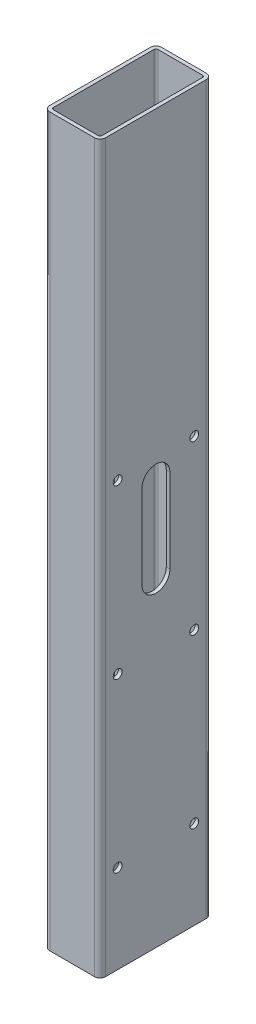
SolidWorks part; units mm, degrees
material "6061-T6 (SS)"
ref_plane "Front Plane" through (0, 0, 0) normal (0, 0, 1) x (1, 0, 0)
ref_plane "Top Plane" through (0, 0, 0) normal (0, 1, 0) x (1, 0, 0)
ref_plane "Right Plane" through (0, 0, 0) normal (1, 0, 0) x (0, 0, -1)
sketch "Sketch1" plane through (0, 0, 0) normal (0, 1, 0) x (1, 0, 0)
  line L1 (10.16, -25.4) -> (-10.16, -25.4)
  line L2 (12.7, -22.86) -> (12.7, 22.86)
  line L3 (10.16, 25.4) -> (-10.16, 25.4)
  line L4 (-12.7, -22.86) -> (-12.7, 22.86)
  line L5 (12.7, -25.4) -> (-12.7, 25.4) construction
  line L6 (12.7, 25.4) -> (-12.7, -25.4) construction
  arc A0 (-10.16, -25.4) -> (-12.7, -22.86) centre (-10.16, -22.86) cw
  arc A1 (10.16, -25.4) -> (12.7, -22.86) centre (10.16, -22.86) ccw
  arc A2 (12.7, 22.86) -> (10.16, 25.4) centre (10.16, 22.86) ccw
  arc A3 (-10.16, 25.4) -> (-12.7, 22.86) centre (-10.16, 22.86) ccw
  point P0 (0, 0)
  dimension "D3" = 2.54
  dimension "D1" = 25.4
  dimension "D2" = 50.8
extrude "Extrude-Thin1" add sketch "Sketch1" against normal blind 330.2 thin thin type one direction reverse wall 1.651
sketch "Sketch2" plane through (-12.7, 0, 0) normal (-1, 0, 0) x (0, 0, 1)
  line L0 (0, -146.2416) -> (0, -281.392) construction
  line L3 (-262.7767, -420.7745) -> (-262.7767, -434.1095) construction
  line L4 (6.6675, -146.2416) -> (6.6675, -281.392)
  line L5 (-6.6675, -146.2416) -> (-6.6675, -281.392)
  line L6 (-263.9645, -427.442) -> (-128.814, -427.442) construction
  line L7 (-128.814, -427.442) -> (0, -151.1994) construction
  line L8 (0, -275.042) -> (-263.9645, -427.442) construction
  line L10 (-122.464, -420.7745) -> (-270.3145, -420.7745) construction
  line L11 (-270.3145, -434.1095) -> (-122.464, -434.1095) construction
  arc A2 (6.6675, -146.2416) -> (-6.6675, -146.2416) centre (0, -146.2416) ccw
  arc A3 (-6.6675, -281.392) -> (6.6675, -281.392) centre (0, -281.392) ccw
  point P3 (0, -213.8168)
  point P18 (-262.7767, -427.442)
  dimension "D5" = 13.335
  dimension "D2" = 65
  dimension "D3" = 30
  dimension "D4" = 304.8
  dimension "D6" = 6.35
extrude "Cut-Extrude1" cut sketch "Sketch2" against normal up to next
sketch "Sketch5" plane through (12.7, 0, 0) normal (1, 0, 0) x (0, 0, -1)
  line L0 (0, -146.2416) -> (0, -184.3416) construction
  line L1 (6.35, -146.2416) -> (6.35, -184.3416)
  line L2 (-6.35, -146.2416) -> (-6.35, -184.3416)
  arc A0 (6.35, -146.2416) -> (-6.35, -146.2416) centre (0, -146.2416) ccw
  arc A1 (-6.35, -184.3416) -> (6.35, -184.3416) centre (0, -184.3416) ccw
  arc A2 (6.6675, -146.2416) -> (-6.6675, -146.2416) centre (0, -146.2416) ccw construction
  point P2 (0, -165.2916)
  dimension "D1" = 6.35
  dimension "D2" = 38.1
extrude "Cut-Extrude4" cut sketch "Sketch5" against normal up to next
sketch "Sketch4" plane through (12.7, 0, 0) normal (1, 0, 0) x (0, 0, -1)
  circle A0 centre (-17.399, -290.0168) radius 2.0193 construction
  circle A1 centre (17.399, -290.0168) radius 2.0193 construction
  circle A2 centre (-17.399, -213.8168) radius 2.0193 construction
  circle A3 centre (17.399, -213.8168) radius 2.0193 construction
  circle A4 centre (-17.399, -137.6168) radius 2.0193 construction
  circle A5 centre (17.399, -137.6168) radius 2.0193 construction
  circle A6 centre (-17.399, -290.0168) radius 2.0193
  circle A7 centre (17.399, -290.0168) radius 2.0193
  circle A8 centre (-17.399, -213.8168) radius 2.0193
  circle A9 centre (17.399, -213.8168) radius 2.0193
  circle A10 centre (-17.399, -137.6168) radius 2.0193
  circle A11 centre (17.399, -137.6168) radius 2.0193
extrude "Cut-Extrude3" cut sketch "Sketch4" against normal through all
